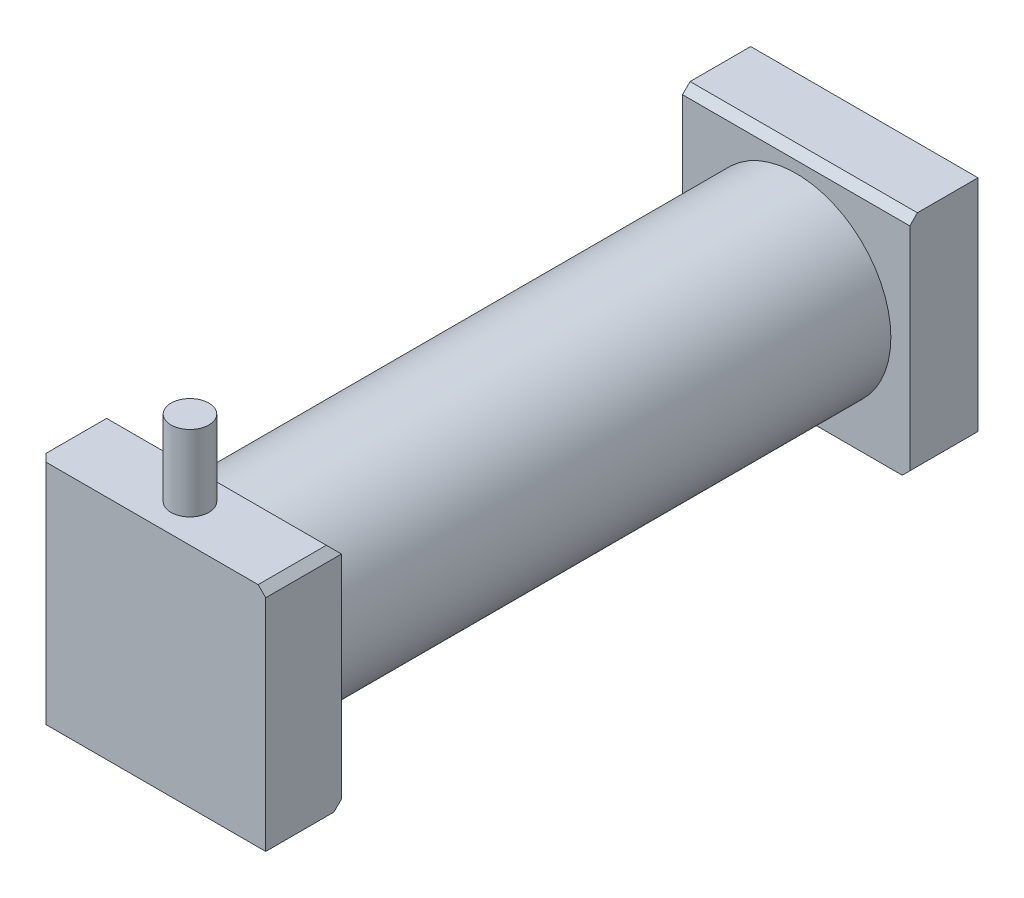
SolidWorks part; units mm, degrees
ref_plane "前视基准面" through (0, 0, 0) normal (0, 0, 1) x (1, 0, 0)
ref_plane "上视基准面" through (0, 0, 0) normal (0, 1, 0) x (1, 0, 0)
ref_plane "右视基准面" through (0, 0, 0) normal (1, 0, 0) x (0, 0, -1)
other "Configuration Table"
sketch "Sketch1" plane through (0, 0, 0) normal (0, 0, 1) x (1, 0, 0)
  circle A0 centre (0, 0) radius 25
extrude "Boss-Extrude1" add sketch "Sketch1" along normal blind 150
sketch "Sketch2" plane through (0, 0, 0) normal (0, 0, 1) x (1, 0, 0)
  line L1 (-30, -30) -> (30, -30)
  line L2 (-30, -30) -> (-30, 30)
  line L3 (-30, 30) -> (30, 30)
  line L4 (30, -30) -> (30, 30)
  line L5 (-30, -30) -> (30, 30) construction
  line L6 (-30, 30) -> (30, -30) construction
  point P0 (0, 0)
extrude "Boss-Extrude2" add sketch "Sketch2" against normal blind 20
ref_plane "Plane1" through (0, 0, 150) normal (0, 0, 1) x (1, 0, 0)
sketch "Sketch3" plane through (0, 0, 150) normal (0, 0, 1) x (1, 0, 0)
  line L1 (-30, -30) -> (30, -30)
  line L2 (-30, -30) -> (-30, 30)
  line L3 (-30, 30) -> (30, 30)
  line L4 (30, -30) -> (30, 30)
  line L5 (-30, -30) -> (30, 30) construction
  line L6 (-30, 30) -> (30, -30) construction
  point P0 (0, 0)
extrude "Boss-Extrude3" add sketch "Sketch3" along normal blind 20
ref_plane "Plane2" through (0, -30, 0) normal (0, 1, 0) x (1, 0, 0)
sketch "Sketch4" plane through (0, -30, 0) normal (0, 1, 0) x (1, 0, 0)
  circle A0 centre (0, 10) radius 5
extrude "Cut-Extrude1" cut sketch "Sketch4" along normal blind 20
ref_plane "Plane3" through (0, 30, 0) normal (0, 1, 0) x (1, 0, 0)
sketch "Sketch5" plane through (0, 30, 0) normal (0, 1, 0) x (1, 0, 0)
  circle A0 centre (0, -160) radius 5
extrude "Boss-Extrude4" add sketch "Sketch5" along normal blind 20
chamfer "Chamfer1" distance 2 angle 45 4 edges at (-30, -30, -10) (-30, 30, -10) (30, -30, -10) (30, 0, -20)
chamfer "Chamfer2" distance 2 angle 45 4 edges at (30, 30, 160) (0, -30, 150) (-30, 0, 170) (-30, 30, 160)
ref_plane "bottom_side_face" through (0, -30, 0) normal (0, 1, 0) x (1, 0, 0)
ref_plane "top_side_face" through (0, 30, 0) normal (0, 1, 0) x (1, 0, 0)
sketch3d "3DSketch1"
  line L0 (0, -30, -10) -> (0, 0, -10) construction
ref_axis "bottom_hole_axis" through (0, -30, -10) along (0, 1, 0)
sketch3d "3DSketch2"
  line L0 (0, 30, 160) -> (0, 50, 160) construction
ref_axis "top_pin_axis" through (0, 30, 160) along (0, 1, 0)
sketch "Sketch6" plane through (0, 0, 0) normal (0, 0, 1) x (1, 0, 0)
  circle A0 centre (0, 0) radius 25
extrude "Boss-Extrude5" add sketch "Sketch6" along normal blind 150
sketch "Sketch7" plane through (0, 0, 0) normal (0, 0, 1) x (1, 0, 0)
  line L0 (33, 30) -> (-33, 30) construction
  line L1 (-30, -30) -> (30, -30)
  line L2 (-30, -30) -> (-30, 30)
  line L3 (-30, 30) -> (30, 30)
  line L4 (30, -30) -> (30, 30)
  line L5 (-30, -30) -> (30, 30) construction
  line L6 (-30, 30) -> (30, -30) construction
  point P0 (0, 0)
extrude "Boss-Extrude6" add sketch "Sketch7" against normal blind 20
ref_plane "Plane6" through (0, 0, 150) normal (0, 0, 1) x (1, 0, 0)
sketch "Sketch8" plane through (0, 0, 150) normal (0, 0, 1) x (1, 0, 0)
  line L0 (33, 30) -> (-33, 30) construction
  line L1 (-30, -30) -> (30, -30)
  line L2 (-30, -30) -> (-30, 30)
  line L3 (-30, 30) -> (30, 30)
  line L4 (30, -30) -> (30, 30)
  line L5 (-30, -30) -> (30, 30) construction
  line L6 (-30, 30) -> (30, -30) construction
  point P0 (0, 0)
extrude "Boss-Extrude7" add sketch "Sketch8" along normal blind 20
ref_plane "Plane7" through (0, -30, 0) normal (0, 1, 0) x (1, 0, 0)
sketch "Sketch9" plane through (0, -30, 0) normal (0, 1, 0) x (1, 0, 0)
  circle A0 centre (0, 10) radius 5
extrude "Cut-Extrude2" cut sketch "Sketch9" along normal blind 20
ref_plane "Plane8" through (0, 30, 0) normal (0, 1, 0) x (1, 0, 0)
sketch "Sketch10" plane through (0, 30, 0) normal (0, 1, 0) x (1, 0, 0)
  circle A0 centre (0, -160) radius 5
extrude "Boss-Extrude8" add sketch "Sketch10" along normal blind 20
chamfer "Chamfer3" distance 2 angle 45 5 edges at (30, -30, -10) (-30, 0, -20) (0, -30, -20) (30, 0, -20) (-30, 0, 0)
chamfer "Chamfer4" distance 2 angle 45 4 edges at (0, 30, 170) (30, 30, 160) (0, -30, 150) (-30, 0, 150)
ref_plane "Plane9" through (0, -30, 0) normal (0, 1, 0) x (1, 0, 0)
ref_plane "Plane10" through (0, 30, 0) normal (0, 1, 0) x (1, 0, 0)
sketch3d "3DSketch3"
  line L0 (0, -30, -10) -> (0, 0, -10) construction
ref_axis "Axis3" through (0, -30, -10) along (0, 1, 0)
sketch3d "3DSketch4"
  line L0 (0, 30, 160) -> (0, 50, 160) construction
ref_axis "Axis4" through (0, 30, 160) along (0, 1, 0)
sketch "Sketch11" plane through (0, 0, 0) normal (0, 0, 1) x (1, 0, 0)
  circle A0 centre (0, 0) radius 25
extrude "Boss-Extrude9" add sketch "Sketch11" along normal blind 150
sketch "Sketch12" plane through (0, 0, 0) normal (0, 0, 1) x (1, 0, 0)
  line L0 (33, 30) -> (-33, 30) construction
  line L1 (-30, -30) -> (30, -30)
  line L2 (-30, -30) -> (-30, 30)
  line L3 (-30, 30) -> (30, 30)
  line L4 (30, -30) -> (30, 30)
  line L5 (-30, -30) -> (30, 30) construction
  line L6 (-30, 30) -> (30, -30) construction
  point P0 (0, 0)
extrude "Boss-Extrude10" add sketch "Sketch12" against normal blind 20
ref_plane "Plane11" through (0, 0, 150) normal (0, 0, 1) x (1, 0, 0)
sketch "Sketch13" plane through (0, 0, 150) normal (0, 0, 1) x (1, 0, 0)
  line L0 (33, 30) -> (-33, 30) construction
  line L1 (-30, -30) -> (30, -30)
  line L2 (-30, -30) -> (-30, 30)
  line L3 (-30, 30) -> (30, 30)
  line L4 (30, -30) -> (30, 30)
  line L5 (-30, -30) -> (30, 30) construction
  line L6 (-30, 30) -> (30, -30) construction
  point P0 (0, 0)
extrude "Boss-Extrude11" add sketch "Sketch13" along normal blind 20
ref_plane "Plane12" through (0, -30, 0) normal (0, 1, 0) x (1, 0, 0)
sketch "Sketch14" plane through (0, -30, 0) normal (0, 1, 0) x (1, 0, 0)
  circle A0 centre (0, 10) radius 5
extrude "Cut-Extrude3" cut sketch "Sketch14" along normal blind 20
ref_plane "Plane13" through (0, 30, 0) normal (0, 1, 0) x (1, 0, 0)
sketch "Sketch15" plane through (0, 30, 0) normal (0, 1, 0) x (1, 0, 0)
  circle A0 centre (0, -160) radius 5
extrude "Boss-Extrude12" add sketch "Sketch15" along normal blind 20
chamfer "Chamfer5" distance 2 angle 45 5 edges at (-30, -30, -10) (30, -30, -10) (0, 30, -20) (30, 0, -20) (0, 30, 0)
chamfer "Chamfer6" distance 2 angle 45 5 edges at (-30, 0, 170) (30, 30, 160) (0, -30, 150) (-30, 0, 150) (0, 30, 150)
ref_plane "Plane14" through (0, -30, 0) normal (0, 1, 0) x (1, 0, 0)
ref_plane "Plane15" through (0, 30, 0) normal (0, 1, 0) x (1, 0, 0)
sketch3d "3DSketch5"
  line L0 (0, -30, -10) -> (0, 0, -10) construction
ref_axis "Axis5" through (0, -30, -10) along (0, 1, 0)
sketch3d "3DSketch6"
  line L0 (0, 30, 160) -> (0, 50, 160) construction
ref_axis "Axis6" through (0, 30, 160) along (0, 1, 0)
